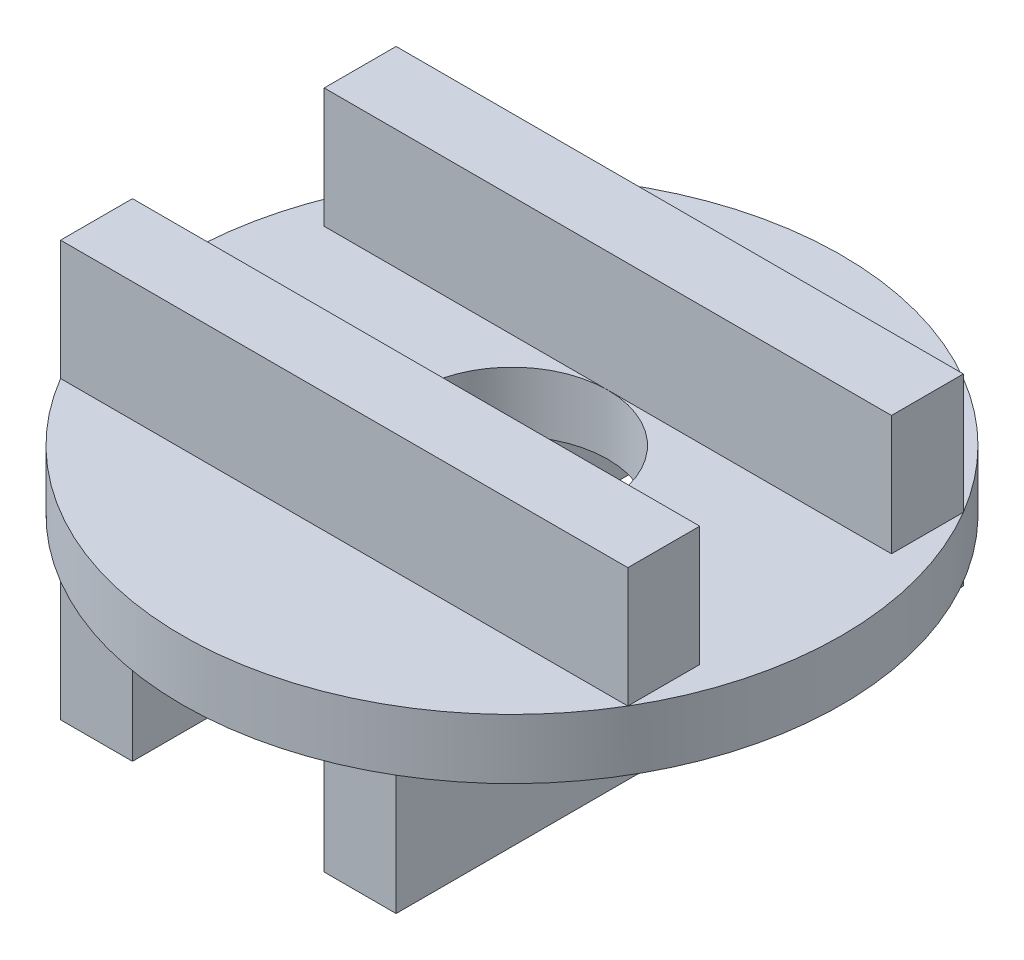
SolidWorks part; units mm, degrees
ref_plane "Front Plane" through (0, 0, 0) normal (0, 0, 1) x (1, 0, 0)
ref_plane "Top Plane" through (0, 0, 0) normal (0, 1, 0) x (1, 0, 0)
ref_plane "Right Plane" through (0, 0, 0) normal (1, 0, 0) x (0, 0, -1)
sketch "Sketch1" plane through (0, 0, 0) normal (0, 1, 0) x (1, 0, 0)
  line L0 (16, 0) -> (16, 52.6213) construction
  line L1 (16, 52.6213) -> (16, -52.6213) construction
  line L2 (0, 61.1631) -> (0, -67.0482) construction
  line L3 (64.2881, 0) -> (-79.3379, 0) construction
  line L4 (16, -52.6213) -> (-16, -52.6213) construction
  line L5 (16, 52.6213) -> (-16, 52.6213) construction
  line L6 (16, 52.6213) -> (60.6179, 52.6213) construction
  line L7 (16, -52.6213) -> (53.2776, -52.6213) construction
  line L8 (28, 47.3392) -> (28, -47.3392)
  line L9 (16, -47.3392) -> (28, -47.3392)
  line L10 (16, -47.3392) -> (16, 47.3392)
  line L11 (16, 47.3392) -> (28, 47.3392)
  line L12 (-56.5817, 16) -> (68.0254, 16) construction
  line L13 (47.3392, 28) -> (-47.3392, 28)
  line L14 (-47.3392, 28) -> (-47.3392, 16)
  line L15 (-47.3392, 16) -> (47.3392, 16)
  line L16 (47.3392, 16) -> (47.3392, 28)
  line L17 (-16, -47.3392) -> (-16, 47.3392)
  line L18 (-16, -47.3392) -> (-28, -47.3392)
  line L19 (-28, 47.3392) -> (-28, -47.3392)
  line L20 (-16, 47.3392) -> (-28, 47.3392)
  line L21 (-47.3392, -16) -> (47.3392, -16)
  line L22 (-47.3392, -28) -> (-47.3392, -16)
  line L23 (47.3392, -28) -> (-47.3392, -28)
  line L24 (47.3392, -16) -> (47.3392, -28)
  circle A0 centre (0, 0) radius 55
  circle A1 centre (0, 0) radius 16
  dimension "D1" = 12
  dimension "D2" = 110
  dimension "D3" = 32
  dimension "D4" = 12
extrude "Boss-Extrude1" add sketch "Sketch1" along normal blind 30 contours L15 L16 L13 L8 | L10 L15 L8 L13 | L17 L15 L10 L13 | L13 L19 L15 L17 | L19 L13 L14 L15 | L23 L19 L21 L22 | L23 L17 L21 L19 | L23 L10 L21 L17 | L23 L8 L21 L10 | L24 L21 L8 L23 region at (37.6696, 0, -22) region at (22, 0, -22) region at (0, 0, -22) region at (-37.6696, 0, -22) region at (-22, 0, -22) region at (37.6696, 0, 22) region at (22, 0, 22) region at (-37.6696, 0, 22) region at (0, 0, 22) region at (-22, 0, 22)
extrude "Boss-Extrude2" add sketch "Sketch1<3>" against normal blind 20 contours L8 L23 L10 L9 | L23 L8 L21 L10 | L10 L21 L8 L15 | L10 L15 L8 L13 | L13 L8 L11 L10 | L17 L23 L19 L18 | L23 L17 L21 L19 | L19 L21 L17 L15 | L13 L19 L15 L17 | L17 L20 L19 L13 region at (22, 0, -37.6696) region at (22, 0, -22) region at (-22, 0, -37.6696) region at (22, 0, 0) region at (-22, 0, -22) region at (22, 0, 22) region at (-22, 0, 0) region at (22, 0, 37.6696) region at (-22, 0, 22) region at (-22, 0, 37.6696)
sketch "Sketch1<3>" plane through (0, 0, 0) normal (0, 1, 0) x (1, 0, 0) same geometry as "Sketch1"
extrude "Boss-Extrude4" add sketch "Sketch1<4>" along normal blind 10 contours L8 A0 L23 | L24 A0 L16 L15 L8 L21 | L13 A0 L8 | L11 A0 L20 L17 L13 L10 | L14 A0 L22 L21 L19 L15 | L23 A0 L19 | L19 A0 L13 | A1 L15 L17 | A1 L17 L21 | A1 L21 L10 | A1 L10 L15 | L13 L8 L11 L10 | L10 L21 L8 L15 | L8 L23 L10 L9 | L19 L21 L17 L15 | L17 L20 L19 L13 | L18 A0 L9 L10 L23 L17 | L17 L23 L19 L18 region at (34.9829, 0, -34.9829) region at (22, 0, -37.6696) region at (0, 0, -41.7412) region at (41.7412, 0, 0) region at (-22, 0, -37.6696) region at (-34.9829, 0, -34.9829) region at (22, 0, 0) region at (-41.7412, 0, 0) region at (12.4261, 0, -12.4261) region at (34.9829, 0, 34.9829) region at (-22, 0, 0) region at (-34.9829, 0, 34.9829) region at (22, 0, 37.6696) region at (12.4261, 0, 12.4261) region at (-12.4261, 0, -12.4261) region at (0, 0, 41.7412) region at (-22, 0, 37.6696) region at (-12.4261, 0, 12.4261)
sketch "Sketch1<4>" plane through (0, 0, 0) normal (0, 1, 0) x (1, 0, 0) same geometry as "Sketch1"
